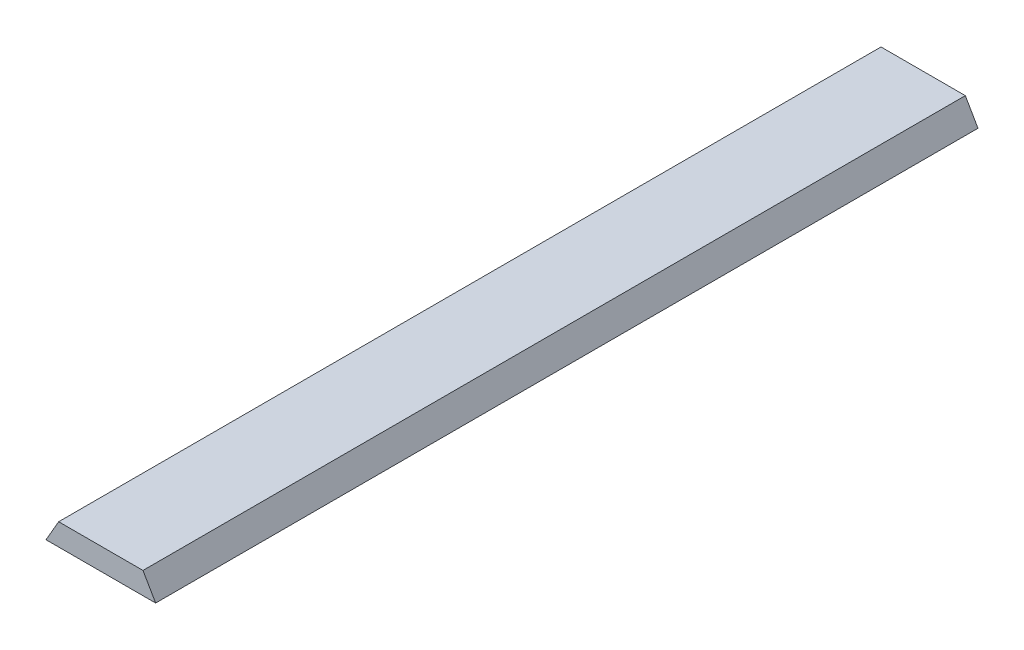
SolidWorks part; units mm, degrees
ref_plane "Front Plane" through (0, 0, 0) normal (0, 0, 1) x (1, 0, 0)
ref_plane "Top Plane" through (0, 0, 0) normal (0, 1, 0) x (1, 0, 0)
ref_plane "Right Plane" through (0, 0, 0) normal (1, 0, 0) x (0, 0, -1)
sketch "Sketch1" plane through (0, 0, 0) normal (0, 0, 1) x (1, 0, 0)
  line L1 (-1, -0.2) -> (1, -0.2)
  line L2 (-1, -0.2) -> (-1, 0.2)
  line L3 (-1, 0.2) -> (1, 0.2)
  line L4 (1, -0.2) -> (1, 0.2)
  line L5 (-1, -0.2) -> (1, 0.2) construction
  line L6 (-1, 0.2) -> (1, -0.2) construction
  point P0 (0, 0)
  dimension "D1" = 2
  dimension "D2" = 0.4
extrude "Boss-Extrude1" add sketch "Sketch1" along normal blind 15
chamfer "Chamfer1" distance 0.4 angle 30 2 edges at (-1, 0.2, 7.5) (1, 0.2, 7.5) first distance on face at (-1, 0, 7.5) first distance on face at (1, 0, 7.5)
